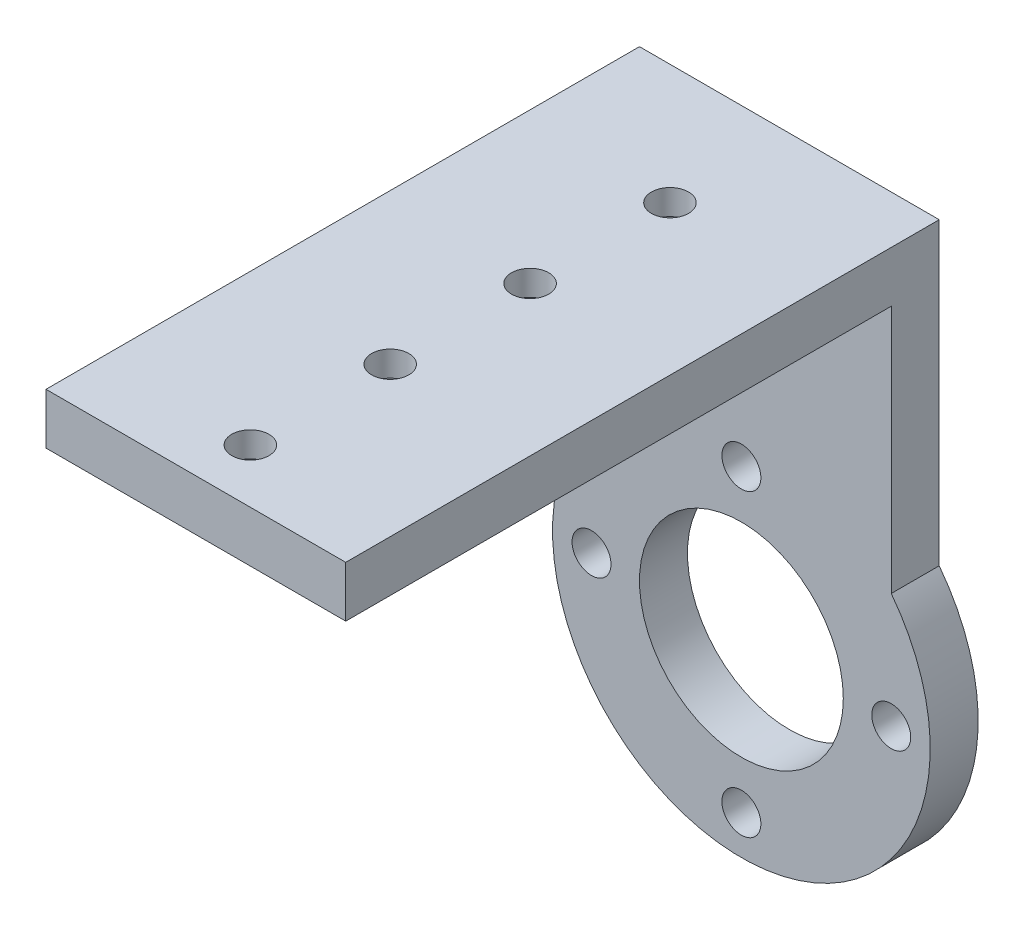
SolidWorks part; units mm, degrees
ref_plane "前视基准面" through (0, 0, 0) normal (0, 0, 1) x (1, 0, 0)
ref_plane "上视基准面" through (0, 0, 0) normal (0, 1, 0) x (1, 0, 0)
ref_plane "右视基准面" through (0, 0, 0) normal (1, 0, 0) x (0, 0, -1)
sketch "草图1" plane through (0, 0, 0) normal (0, 0, 1) x (1, 0, 0)
  line L2 (17.8638, 69.1638) -> (-25, 69.1638)
  line L3 (-25, 69.1638) -> (-25, 28.7351)
  line L4 (-25, 28.7351) -> (-25, 19.1638)
  line L5 (17.8638, 69.1638) -> (25, 69.1638)
  line L6 (25, 69.1638) -> (25, 19.1638)
  circle A0 centre (0, 0) radius 25
  circle A1 centre (0, 0) radius 31.5
  circle A2 centre (0, 25) radius 3.25
  circle A3 centre (-25, 0) radius 3.25
  circle A4 centre (25, 0) radius 3.25
  circle A5 centre (0, -25) radius 3.25
  circle A6 centre (0, 0) radius 17
extrude "凸台-拉伸1" add sketch "草图1" along normal blind 8 contours A1
extrude "切除-拉伸1" cut sketch "草图1<3>" along normal blind 8 contours A2 | A4 | A5 | A3
sketch "草图1<3>" plane through (0, 0, 0) normal (0, 0, 1) x (1, 0, 0) same geometry as "草图1"
extrude "切除-拉伸2" cut sketch "草图1<4>" along normal blind 6 contours A6 region at (0, 0, 0)
sketch "草图1<4>" plane through (0, 0, 0) normal (0, 0, 1) x (1, 0, 0) same geometry as "草图1"
extrude "凸台-拉伸2" add sketch "草图1<5>" along normal blind 4 contours A1 L6 L5 L2 L3 L4 region at (0, 48.3194, 0)
sketch "草图1<5>" plane through (0, 0, 0) normal (0, 0, 1) x (1, 0, 0) same geometry as "草图1"
sketch "草图4" plane through (0, 0, 4) normal (0, 0, 1) x (1, 0, 0)
  line L0 (-25, 69.1638) -> (-25, 60.6638)
  line L1 (-25, 69.1638) -> (-25, 19.1638) construction
  line L2 (-25, 60.6638) -> (25, 60.6638)
  line L3 (25, 69.1638) -> (25, 19.1638) construction
  line L4 (25, 60.6638) -> (25, 69.1638)
  line L5 (25, 69.1638) -> (-25, 69.1638)
extrude "凸台-拉伸3" add sketch "草图4" along normal blind 95
sketch "草图5" plane through (0, 60.6638, 0) normal (0, -1, 0) x (1, 0, 0)
  circle A0 centre (0.0884, 90) radius 3.1
  circle A1 centre (0.0884, 90) radius 6.75
  circle A2 centre (0.0884, 20) radius 3.1
  circle A3 centre (0.0884, 20) radius 6.75
  circle A4 centre (0.0884, 43.333) radius 3.1
  circle A5 centre (0.0884, 43.333) radius 6.75
  circle A6 centre (0.0884, 66.6667) radius 3.1
  circle A7 centre (0.0884, 66.6667) radius 6.75
extrude "切除-拉伸3" cut sketch "草图5" against normal blind 10 contours A0 | A6 | A4 | A2
extrude "切除-拉伸4" cut sketch "草图5<3>" against normal blind 4.3 contours A7 A6 | A5 A4 | A3 A2 | A1 region at (-6.4707, 60.6638, 20) region at (-6.4707, 60.6638, 43.333) region at (-6.4707, 60.6638, 66.6667)
sketch "草图5<3>" plane through (0, 60.6638, 0) normal (0, -1, 0) x (1, 0, 0) same geometry as "草图5"
extrude "凸台-拉伸4" add sketch "草图1<7>" along normal blind 8 contours A1 L6 L5 L2 L3 L4 region at (0, 48.3194, 0)
sketch "草图1<7>" plane through (0, 0, 0) normal (0, 0, 1) x (1, 0, 0) same geometry as "草图1"
extrude "切除-拉伸5" cut sketch "草图1<8>" along normal blind 8 contours A6
sketch "草图1<8>" plane through (0, 0, 0) normal (0, 0, 1) x (1, 0, 0) same geometry as "草图1"
